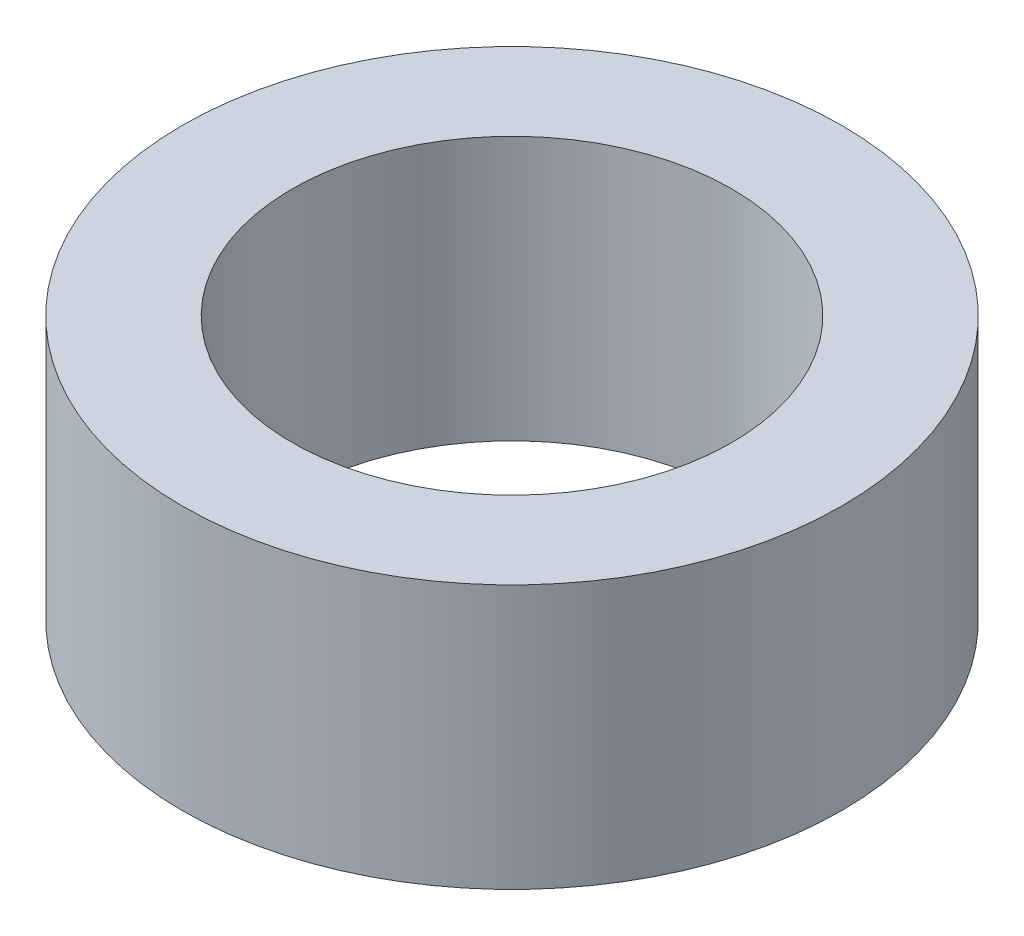
SolidWorks part; units mm, degrees
material "PVC Rigid"
ref_plane "Front Plane" through (0, 0, 0) normal (0, 0, 1) x (1, 0, 0)
ref_plane "Top Plane" through (0, 0, 0) normal (0, 1, 0) x (1, 0, 0)
ref_plane "Right Plane" through (0, 0, 0) normal (1, 0, 0) x (0, 0, -1)
sketch "Sketch1" plane through (0, 0, 0) normal (0, 1, 0) x (1, 0, 0)
  circle A0 centre (0, 0) radius 9.525
  circle A1 centre (0, 0) radius 6.35
  dimension "D1" = 19.05
  dimension "D2" = 12.7
extrude "Boss-Extrude1" add sketch "Sketch1" along normal blind 7.62
